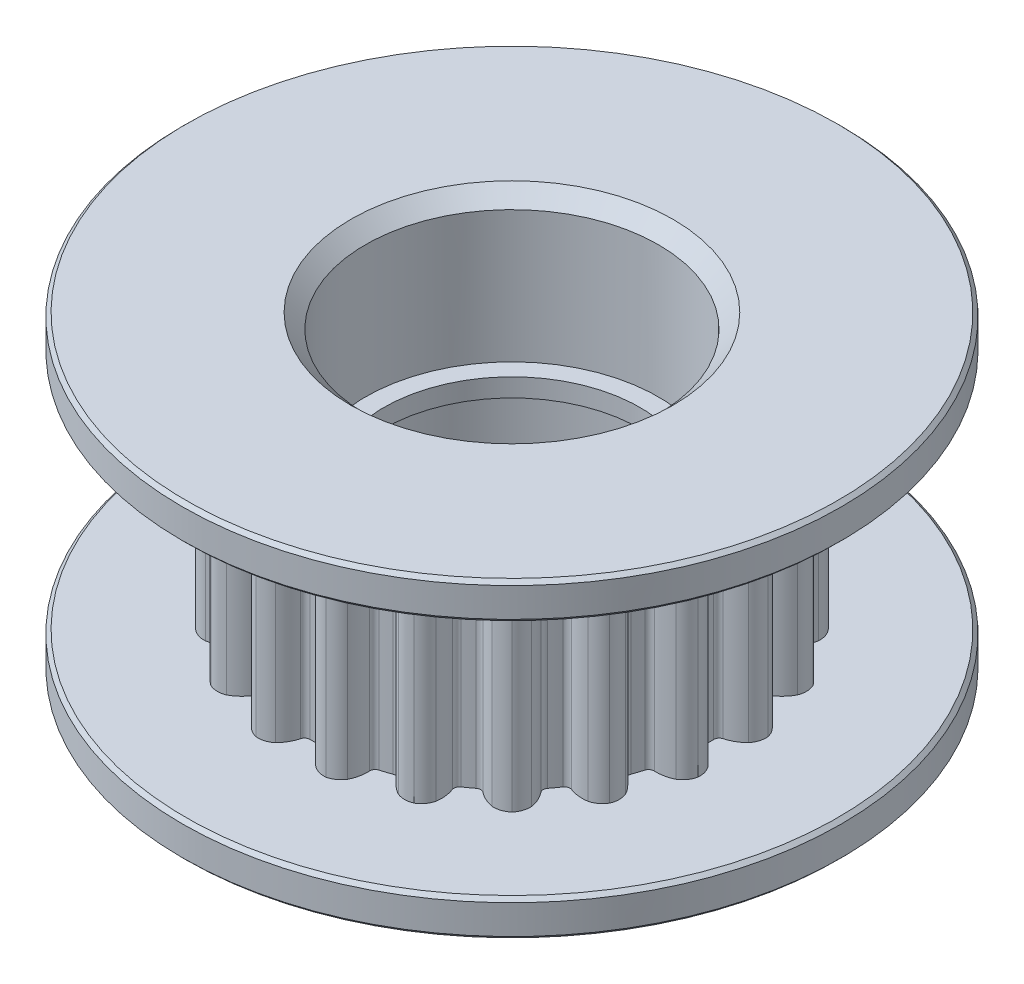
SolidWorks part; units mm, degrees
material "6061 Alloy"
ref_plane "Front Plane" through (0, 0, 0) normal (0, 0, 1) x (1, 0, 0)
ref_plane "Top Plane" through (0, 0, 0) normal (0, 1, 0) x (1, 0, 0)
ref_plane "Right Plane" through (0, 0, 0) normal (1, 0, 0) x (0, 0, -1)
sketch "BodyS" plane through (0, 0, 0) normal (0, 0, 1) x (1, 0, 0)
  line L0 (6.11, -3.25) -> (6.11, 3.25)
  line L1 (6.11, 3.25) -> (9, 3.25)
  line L2 (9, 3.25) -> (9, 4.25)
  line L3 (9, 4.25) -> (4, 4.25)
  line L4 (4, 4.25) -> (4, 0.25)
  line L5 (4, 0.25) -> (3.5, 0.25)
  line L6 (3.5, 0.25) -> (3.5, -0.25)
  line L7 (3.5, -0.25) -> (4, -0.25)
  line L8 (4, -0.25) -> (4, -4.25)
  line L9 (4, -4.25) -> (9, -4.25)
  line L10 (9, -4.25) -> (9, -3.25)
  line L11 (9, -3.25) -> (6.11, -3.25)
  line L12 (0, 0) -> (3.5, 0) construction
  line L13 (0, 4.25) -> (0, -4.25) construction
  dimension "BearingOD" = 8
  dimension "Height" = 8.5
  dimension "FlangeHeight" = 1
  dimension "BearingHeight" = 4
  dimension "BearingRestDiaControl" = 0.5
  dimension "RefBodyInnerDiameter" = 7
  dimension "FlangeDiaControl" = 5
  dimension "RefFlangeDia" = 18
  dimension "BeltPathDiaControl" = 2.11
  dimension "RefBeltPathDia" = 12.22
revolve "Body" add sketch "BodyS" angle 360 about L13
sketch "GT2ProfileS" plane through (0, 0, 0) normal (0, 1, 0) x (1, 0, 0)
  line L1 (0, -6.11) -> (0, -5.36) construction
  line L2 (-0.9955, -6.0283) -> (-0.8733, -5.2884) construction
  line L3 (0, 0) -> (-0.8733, -5.2884) construction
  line L4 (0.9955, -6.0283) -> (0, 0) construction
  arc A3 (0.2997, -5.4688) -> (0.1507, -5.3579) centre (0.1549, -5.5078) ccw
  arc A4 (-0.9955, -6.0283) -> (0.9955, -6.0283) centre (0, 0) ccw
  arc A5 (-0.2997, -5.4688) -> (-0.1507, -5.3579) centre (-0.1549, -5.5078) cw
  arc A6 (-0.2997, -5.4688) -> (-0.5497, -5.907) centre (-1.2653, -5.2085) cw
  circle A7 centre (0, 0) radius 6.11 construction
  arc A8 (-0.1507, -5.3579) -> (0.1507, -5.3579) centre (0, 0) ccw
  arc A9 (-0.5497, -5.907) -> (-0.9955, -6.0283) centre (-0.9051, -5.4808) cw
  arc A10 (0.2997, -5.4688) -> (0.5497, -5.907) centre (1.2653, -5.2085) ccw
  arc A11 (0.5497, -5.907) -> (0.9955, -6.0283) centre (0.9051, -5.4808) ccw
  circle A12 centre (0, 0) radius 5.36 construction
  dimension "BottomRadius" = 0.15
  dimension "MidRadius" = 1
  dimension "TopRadius" = 0.555
  dimension "Height" = 0.75
  dimension "XDistMidRadius" = 0.4
  dimension "ArcLengthAngle" = 18.755
  dimension "ArcLength" = 2
sketch "ThruBoreS" [suppressed] plane through (0, 0, 0) normal (0, 1, 0) x (1, 0, 0)
  circle A0 centre (0, 0) radius 4
  circle A2 centre (0, 0) radius 4 construction
extrude "ThruBore" [suppressed] cut sketch "ThruBoreS" against normal through all both and the other way through all
extrude "GT2Profile" cut sketch "GT2ProfileS" against normal up to surface and the other way up to surface up to face at (0, -3.25, 6.11) other way up to face at (0, 3.25, 9)
pattern_circular "GT2 Groove CP" count 20 over 360 about axis through (0, 4.25, 0) along (0, 1, 0) of "GT2Profile"
chamfer "InnerC" distance 0.4 angle 45 2 edges at (0, -4.25, 4) (0, 4.25, 4)
chamfer "OuterC" distance 0.1 angle 45 4 edges at (0, -4.25, 9) (0, -3.25, 9) (0, 3.25, 9) (0, 4.25, 9)
equation "\"NumTeeth@GT2 Groove CP\"=int(360/\"ArcLengthAngle@GT2ProfileS\")+1"
